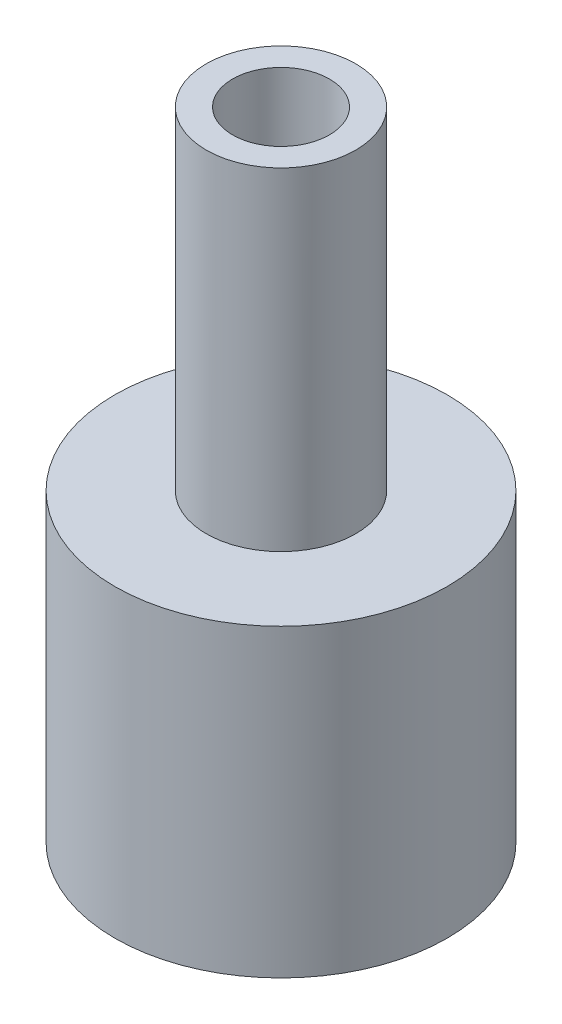
SolidWorks part; units mm, degrees
material "Titanium Ti-8Mn, Annealed"
ref_plane "Front Plane" through (0, 0, 0) normal (0, 0, 1) x (1, 0, 0)
ref_plane "Top Plane" through (0, 0, 0) normal (0, 1, 0) x (1, 0, 0)
ref_plane "Right Plane" through (0, 0, 0) normal (1, 0, 0) x (0, 0, -1)
sketch "Sketch1" plane through (0, 0, 0) normal (0, 1, 0) x (1, 0, 0)
  circle A0 centre (0, 0) radius 1.35
  dimension "D1" = 2.7
extrude "Boss-Extrude1" add sketch "Sketch1" along normal mid plane 11.5 contours A0
sketch "Sketch2" plane through (0, -5.75, 0) normal (0, -1, 0) x (1, 0, 0)
  circle A0 centre (0, 0) radius 3
  dimension "D1" = 6
extrude "Boss-Extrude2" add sketch "Sketch2" against normal blind 5.5
sketch "Sketch3" plane through (0, -5.75, 0) normal (0, -1, 0) x (1, 0, 0)
  circle A0 centre (0, 0) radius 0.875
  dimension "D1" = 1.75
extrude "Cut-Extrude1" cut sketch "Sketch3" against normal through all both and the other way through all
